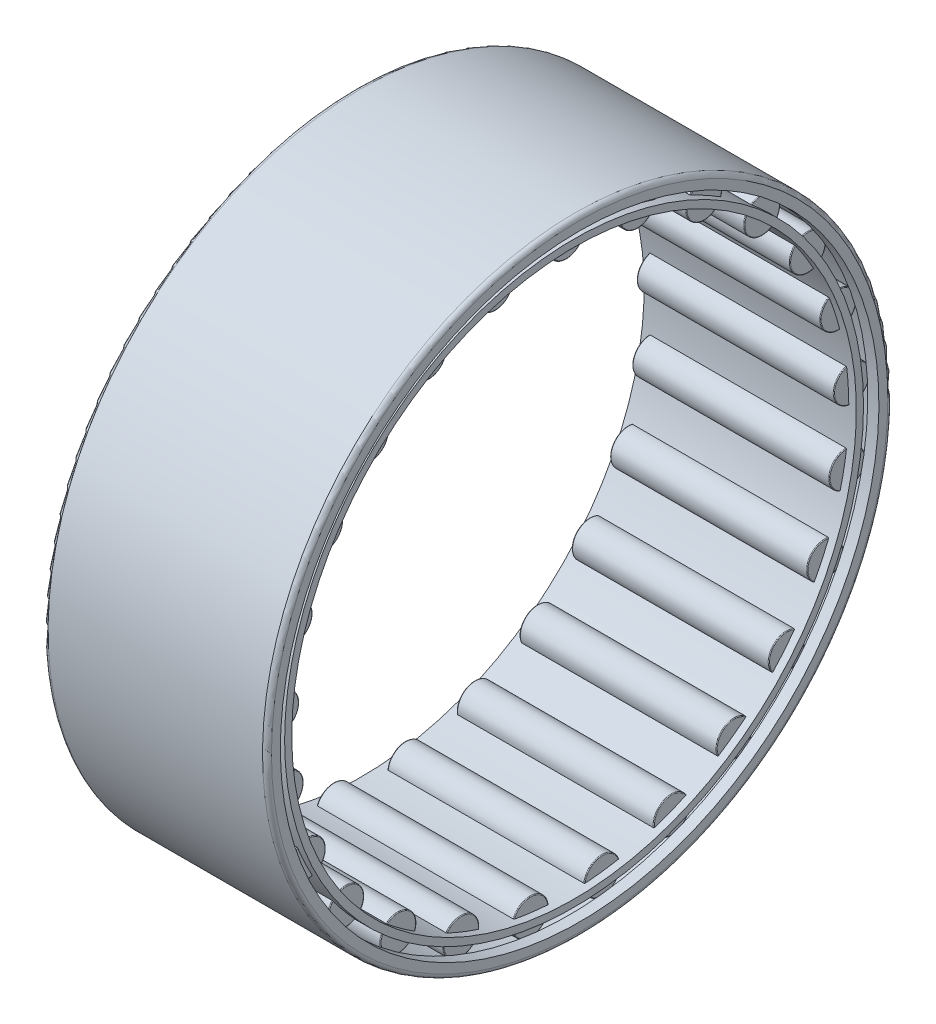
SolidWorks part; units mm, degrees
ref_plane "Plane1" through (0, 0, 0) normal (0, 0, 1) x (1, 0, 0)
ref_plane "Plane2" through (0, 0, 0) normal (0, 1, 0) x (1, 0, 0)
ref_plane "Plane3" through (0, 0, 0) normal (1, 0, 0) x (0, 0, -1)
sketch "Clipboard" plane through (0, 0, 0) normal (0, 0, 1) x (1, 0, 0)
  line L0 (-10, 0) -> (10, 0) construction
  line L1 (0, 0) -> (20.2657, -9.45)
  line L2 (0, 0) -> (36.8323, 17.1752)
  line L3 (0, 0) -> (20.2657, -9.45)
  line L4 (0, 0) -> (-76.2, -2.661)
  dimension "BallCLRad" = 40.64
  dimension "Bore" = 76.2
sketch "InnRacSke" plane through (0, 0, 0) normal (0, 0, 1) x (1, 0, 0)
  line L0 (-14.2875, 42.545) -> (-15.875, 42.545)
  line L1 (-15.875, 42.545) -> (-15.875, 43.815)
  line L2 (-15.24, 44.45) -> (15.24, 44.45)
  line L4 (15.875, 43.815) -> (15.875, 42.545)
  line L5 (15.875, 42.545) -> (14.2875, 42.545)
  line L6 (14.2875, 42.545) -> (14.2875, 43.18)
  line L7 (14.2875, 43.18) -> (-14.2875, 43.18)
  line L8 (-14.2875, 43.18) -> (-14.2875, 42.545)
  line L9 (-31.75, 0) -> (31.75, 0) construction
  arc A0 (-15.875, 43.815) -> (-15.24, 44.45) centre (-15.24, 43.815) cw
  arc A2 (15.24, 44.45) -> (15.875, 43.815) centre (15.24, 43.815) cw
  dimension "D1" = 86.36
revolve "Race" add sketch "InnRacSke" angle 360 about L9 reverse direction yes
sketch "RolDetSke" plane through (0, 0, 0) normal (0, 0, 1) x (1, 0, 0)
  line L0 (-14.0018, 43.0789) -> (-14.0017, 40.64)
  line L1 (-14.0017, 40.64) -> (14.0017, 40.64)
  line L2 (14.0017, 40.64) -> (14.0018, 43.0789)
  line L3 (13.9001, 43.1805) -> (-13.9001, 43.1805)
  line L4 (-28.575, 40.64) -> (28.575, 40.64) construction
  arc A0 (14.0018, 43.0789) -> (13.9001, 43.1805) centre (13.9001, 43.0789) ccw
  arc A1 (-13.9001, 43.1805) -> (-14.0018, 43.0789) centre (-13.9001, 43.0789) ccw
  dimension "Roller_length" = 28.0035
  dimension "Roller_diameter" = 5.081
revolve "RollerDetailed" add sketch "RolDetSke" angle 360 about L4 reverse direction yes
ref_axis "Axis1" through (-50, 0, 0) along (1, 0, 0)
sketch "CagSpiSke" plane through (0, 0, 0) normal (0, 0, 1) x (1, 0, 0)
  line L0 (15.0812, 40.1319) -> (15.0812, 41.1481)
  line L1 (15.0812, 41.1481) -> (-15.0813, 41.1481)
  line L2 (-15.0813, 41.1481) -> (-15.0813, 40.1319)
  line L3 (-15.0813, 40.1319) -> (15.0812, 40.1319)
  line L4 (-31.75, 0) -> (31.75, 0) construction
  dimension "D2" = 80.2638
  dimension "halfWidth" = 15.0813
revolve "CageSpine" add sketch "CagSpiSke" angle 360 about L4
pattern_circular "RollersDetailed" count 25 every 14.4 about axis through (-50, 0, 0) along (1, 0, 0) of "RollerDetailed"
sketch "RolSimSke" plane through (0, 0, 0) normal (0, 0, 1) x (1, 0, 0)
  line L0 (-25.4, 0) -> (25.4, 0) construction
  line L2 (-13.9001, 43.181) -> (13.9001, 43.181)
  line L3 (-14.0018, 43.0794) -> (-14.0018, 38.2016)
  line L4 (-13.9001, 38.1) -> (13.9001, 38.1)
  line L5 (14.0017, 43.0794) -> (14.0017, 38.2016)
  arc A0 (-14.0018, 38.2016) -> (-13.9001, 38.1) centre (-13.9001, 38.2016) ccw
  arc A1 (-13.9001, 43.181) -> (-14.0018, 43.0794) centre (-13.9001, 43.0794) ccw
  arc A2 (14.0017, 43.0794) -> (13.9001, 43.181) centre (13.9001, 43.0794) ccw
  arc A3 (13.9001, 38.1) -> (14.0017, 38.2016) centre (13.9001, 38.2016) ccw
  point P10 (-14.0018, 38.1)
  point P15 (14.0017, 43.181)
  point P18 (14.0017, 38.1)
  dimension "D1" = 0.1016
  dimension "Bore" = 76.2
  dimension "Roller_length" = 28.0035
  dimension "Roller_diameter" = 5.081
  dimension "halfWidth" = 14.0017
revolve "RollersSimplified" [suppressed] add sketch "RolSimSke" angle 360 about L0
equation "\"BallCLRad@Clipboard\" =  ( \"D1@InnRacSke\" + \"Bore@Clipboard\" )  / 4"
equation "\"RollerCLRad@RolDetSke\" = \"BallCLRad@Clipboard\""
equation "\"halfCyl@InnRacSke\" = \"Cyl_Len@InnRacSke\" / 2"
equation "\"Roller_length@RolDetSke\" = \"Cyl_Len@InnRacSke\" * .98"
equation "\"halfLength@RolDetSke\" = \"Roller_length@RolDetSke\" / 2"
equation "\"Roller_diameter@RolDetSke\" =  ( \"D1@InnRacSke\" - \"Bore@Clipboard\" )  / 2 + .001"
equation "\"Roller_radius@RolDetSke\" = \"Roller_diameter@RolDetSke\" / 50"
equation "\"Cage_width@CagSpiSke\" =  ( \"Cyl_Len@InnRacSke\" + \"Width@InnRacSke\" )  / 2"
equation "\"halfWidth@CagSpiSke\" = \"Cage_width@CagSpiSke\" / 2"
equation "\"Cage_thickness@CagSpiSke\"  = \"Roller_diameter@RolDetSke\" / 5"
equation "\"D2@CagSpiSke\" =  \"RollerCLRad@RolDetSke\" * 2 - \"Cage_thickness@CagSpiSke\""
equation "\"Roller_length@RolSimSke\" = \"Cyl_Len@InnRacSke\" * .98"
equation "\"halfWidth@RolSimSke\" = \"Roller_length@RolSimSke\" / 2"
equation "\"D1@RolSimSke\" = \"Roller_radius@RolDetSke\""
equation "\"Roller_diameter@RolSimSke\" =  ( \"D1@InnRacSke\" - \"Bore@Clipboard\" )  / 2 + .001"
equation "\"Bore@RolSimSke\" = \"Bore@Clipboard\""
equation "\"Max_count@Clipboard\" = int( 3.14159265 / atn(( \"Roller_diameter@RolDetSke\" / 2) / sqr( \"RollerCLRad@RolDetSke\"  *  \"RollerCLRad@RolDetSke\" - ( \"Roller_diameter@RolDetSke\" / 2) *  ( \"Roller_diameter@RolDetSke\" / 2))))"
equation "\"Max_count@Clipboard\" = ((sgn( \"Max_count@Clipboard\" - \"Count@Clipboard\" )-1)*( \"Max_count@Clipboard\" - \"Count@Clipboard\" ))/-2+ \"Count@Clipboard\""
equation "\"Count@RollersDetailed\" = int( \"Show_count@Clipboard\" ) "
equation "\"Count@RollersDetailed\" = ((sgn( \"Count@RollersDetailed\" - \"Max_count@Clipboard\" )-1)*( \"Count@RollersDetailed\" - \"Max_count@Clipboard\" ))/-2+ \"Max_count@Clipboard\""
equation "\"Count@RollersDetailed\" = ((sgn( \"Count@RollersDetailed\" - \"Min_count@Clipboard\" )+1)*( \"Count@RollersDetailed\" - \"Min_count@Clipboard\"))/2 +\"Min_count@Clipboard\""
equation "\"Angle@RollersDetailed\" = 360.0 / \"Max_count@Clipboard\""
equation "\"Angle@CageSpine\" =  \"Angle@RollersDetailed\" * ( \"Count@RollersDetailed\" -1 + int( \"Count@RollersDetailed\" / \"Max_count@Clipboard\" ) )  + 0.001 -  int( \"Count@RollersDetailed\" / \"Max_count@Clipboard\" ) * 0.001"
equation "\"Angle@CageSpine\" =  \"Angle@CageSpine\" * int( \"Min_count@Clipboard\" / 2) + int(1 / \"Min_count@Clipboard\")  * 0.001"
